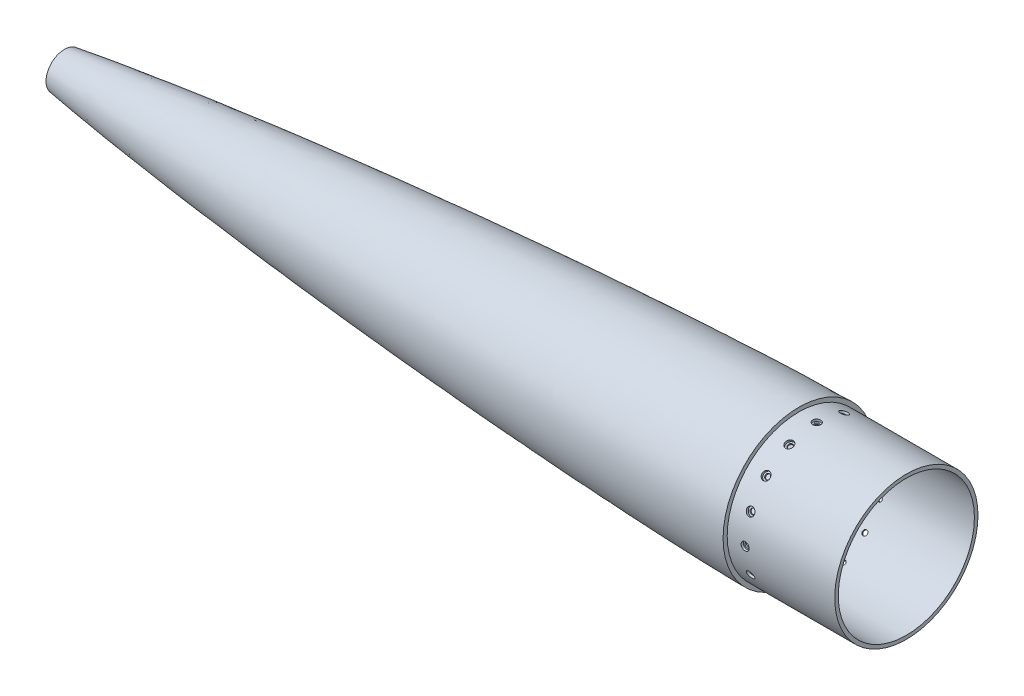
SolidWorks part; units mm, degrees
material "E-Glass Fiber"
ref_plane "Front Plane" through (0, 0, 0) normal (0, 0, 1) x (1, 0, 0)
ref_plane "Top Plane" through (0, 0, 0) normal (0, 1, 0) x (1, 0, 0)
ref_plane "Right Plane" through (0, 0, 0) normal (1, 0, 0) x (0, 0, -1)
sketch "Sketch2" plane through (0, 0, 0) normal (0, 0, 1) x (1, 0, 0)
  line L0 (0, 0) -> (584.2, 0)
  line L1 (584.2, 53.721) -> (584.2, 0)
  spline S0 degree 4 poles (0, 0) (0.0022, 0.0056) (0.0076, 0.0162) (0.0222, 0.0352) (0.0559, 0.0693) (0.1064, 0.1113) (0.1743, 0.1601) (0.2708, 0.2224) (0.3867, 0.2901) (0.5227, 0.3633) (0.6788, 0.4414) (0.9052, 0.5483) (1.2575, 0.7027) (1.8541, 0.9418) (2.9279, 1.3286) (4.8572, 1.9447) (8.3876, 2.9315) (14.9994, 4.5314) (26.6552, 6.951) (46.2509, 10.4452) (73.0277, 14.552) (105.3866, 18.9288) (141.1369, 23.265) (176.9301, 27.2281) (212.7562, 30.881) (248.6088, 34.2635) (284.4837, 37.3993) (320.3781, 40.3033) (356.29, 42.9823) (392.2179, 45.437) (428.1608, 47.6612) (464.1181, 49.6413) (495.5929, 51.1375) (522.5799, 52.2225) (544.3402, 52.9414) (558.9873, 53.3346) (571.0188, 53.5813) (578.5507, 53.684) (582.3169, 53.7167) (584.2, 53.721) knots 0 0 0 0 0 0.000041 0.000081 0.000163 0.000325 0.000488 0.00065 0.000944 0.001239 0.001539 0.001838 0.002649 0.003857 0.005913 0.009607 0.016434 0.028809 0.052217 0.090639 0.151931 0.213222 0.274513 0.335805 0.397096 0.458387 0.519679 0.58097 0.642262 0.703553 0.764844 0.826136 0.887427 0.918073 0.948719 0.974359 0.98718 1 1 1 1 1 construction
  spline S1 degree 4 poles (0, 0) (0.0022, 0.0056) (0.0076, 0.0162) (0.0222, 0.0352) (0.0559, 0.0693) (0.1064, 0.1113) (0.1743, 0.1601) (0.2708, 0.2224) (0.3867, 0.2901) (0.5227, 0.3633) (0.6788, 0.4414) (0.9052, 0.5483) (1.2575, 0.7027) (1.8541, 0.9418) (2.9279, 1.3286) (4.8572, 1.9447) (8.3876, 2.9315) (14.9994, 4.5314) (26.6552, 6.951) (46.2509, 10.4452) (73.0277, 14.552) (105.3866, 18.9288) (141.1369, 23.265) (176.9301, 27.2281) (212.7562, 30.881) (248.6088, 34.2635) (284.4837, 37.3993) (320.3781, 40.3033) (356.29, 42.9823) (392.2179, 45.437) (428.1608, 47.6612) (464.1181, 49.6413) (495.5929, 51.1375) (522.5799, 52.2225) (544.3402, 52.9414) (558.9873, 53.3346) (571.0188, 53.5813) (578.5507, 53.684) (582.3169, 53.7167) (584.2, 53.721) knots 0 0 0 0 0 0.000041 0.000081 0.000163 0.000325 0.000488 0.00065 0.000944 0.001239 0.001539 0.001838 0.002649 0.003857 0.005913 0.009607 0.016434 0.028809 0.052217 0.090639 0.151931 0.213222 0.274513 0.335805 0.397096 0.458387 0.519679 0.58097 0.642262 0.703553 0.764844 0.826136 0.887427 0.918073 0.948719 0.974359 0.98718 1 1 1 1 1
  dimension "D1" = 584.2
revolve "Nosecone Revolve" add sketch "Sketch2" angle 360 about L0
shell "Nosecone Shell" thickness 2.921 removed face at (584.2, 0, 53.721)
sketch "Sketch3" plane through (584.2, 0, 0) normal (1, 0, 0) x (0, 0, -1)
  circle A1 centre (0, 0) radius 50.8
  circle A2 centre (0, 0) radius 48.26
  dimension "D1" = 2.54
  dimension "D2" = 101.6
extrude "Shoulder" add sketch "Sketch3" along normal blind 76.2 and the other way blind 76.2 separate body
combine bodies "Combine1" operation type add bodies to combine 101 102
ref_plane "Tip cutting plane" through (63.5, 0, 0) normal (1, 0, 0) x (0, 0, -1)
sketch "Sketch4" plane through (63.5, 0, 0) normal (1, 0, 0) x (0, 0, -1)
  circle A0 centre (0, 0) radius 57.15
  dimension "D1" = 114.3
extrude "Cut-Extrude1" cut sketch "Sketch4" against normal up to vertex (63.5 mm away) up to point (0, 0, 0)
ref_plane "Hole Plane" through (0, 0, -50.8) normal (0, 0, -1) x (-1, 0, 0)
sketch "Sketch5" plane through (0, 0, -50.8) normal (0, 0, -1) x (-1, 0, 0)
  line L0 (-584.2, 0) -> (-660.4, 0) construction
  line L1 (-584.2, 50.8) -> (-584.2, -50.8) construction
  line L2 (-660.4, 50.8) -> (-660.4, -50.8) construction
  circle A0 centre (-596.9, 0) radius 1.7526
  dimension "D1" = 3.5052
  dimension "D2" = 12.7
extrude "Bulkhead Screws" cut sketch "Sketch5" against normal up to next
pattern_circular "Screw Hole Pattern" count 16 over 360 about axis through (508, 0, 0) along (1, 0, 0) of "Bulkhead Screws" reverse direction yes
sketch "Sketch7" plane through (0, 0, -50.8) normal (0, 0, -1) x (-1, 0, 0)
  circle A0 centre (-596.9, 0) radius 1.7526 construction
  circle A1 centre (-596.9, 0) radius 1.7526
  circle A2 centre (-596.9, 0) radius 2.8702
  dimension "D1" = 5.7404
extrude "Hole CounterSink" cut sketch "Sketch7" against normal blind 1.5875
pattern_circular "CirPattern1" count 16 over 360 about axis through (508, 0, 0) along (1, 0, 0) of "Hole CounterSink"
